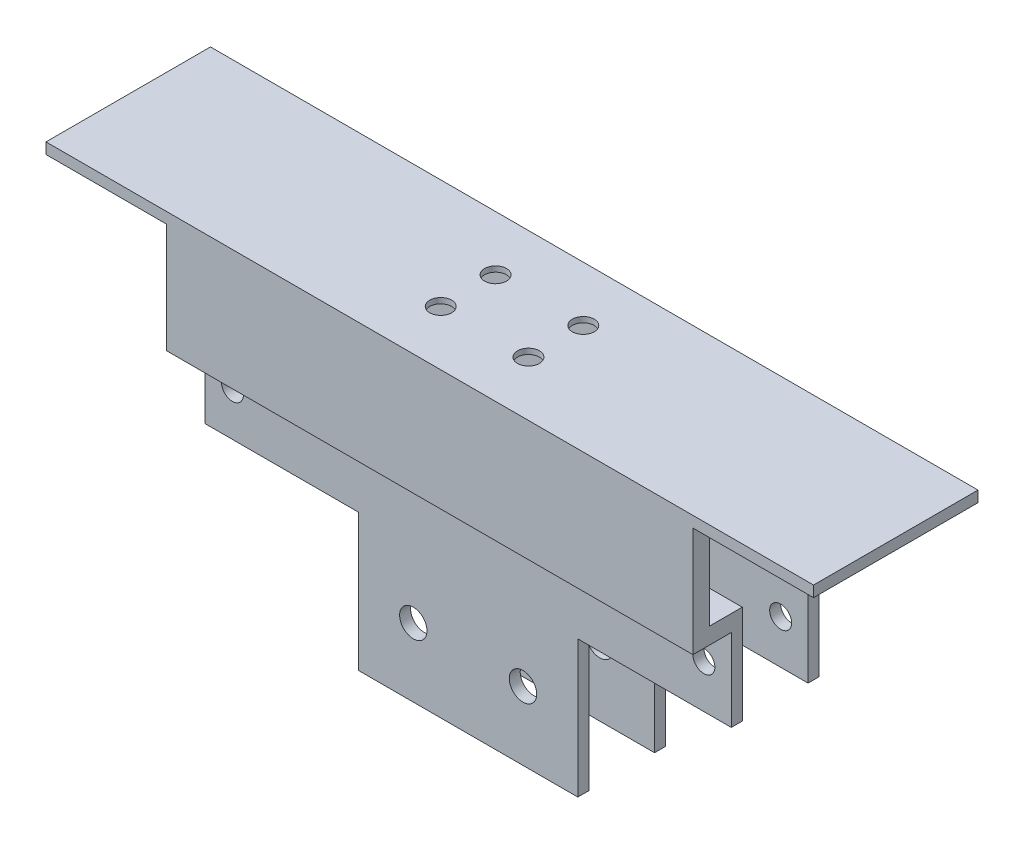
SolidWorks part; units mm, degrees
note: The reader was unsure of these and kept them because the rebuilt part matched: shared geometry of "Profile<3>", "Profile<6>", "Profile<7>", "Profile<8>", "Profile<9>", "Profile<10>", "Sketch3<3>".
ref_plane "Front Plane" through (0, 0, 0) normal (0, 0, 1) x (1, 0, 0)
ref_plane "Top Plane" through (0, 0, 0) normal (0, 1, 0) x (1, 0, 0)
ref_plane "Right Plane" through (0, 0, 0) normal (1, 0, 0) x (0, 0, -1)
sketch "Ref" plane through (0, 0, 0) normal (0, 1, 0) x (1, 0, 0)
  line L1 (-42.7409, 31.4353) -> (97.2591, 31.4353)
  line L2 (-42.7409, 31.4353) -> (-42.7409, 1.4353)
  line L3 (-42.7409, 1.4353) -> (97.2591, 1.4353)
  line L4 (97.2591, 31.4353) -> (97.2591, 1.4353)
  line L5 (-42.7409, 16.4353) -> (97.2591, 16.4353) construction
  point P8 (0, 0)
  dimension "D1" = 30
  dimension "D2" = 140
sketch "Profile" plane through (0, 0, 0) normal (0, 0, 1) x (1, 0, 0)
  line L0 (-32.7409, 0) -> (-32.7409, -35)
  line L1 (-42.7409, 0) -> (97.2591, 0) construction
  line L2 (-42.7409, 0) -> (97.2591, 0) construction
  line L3 (27.2591, 0) -> (27.2591, -85.3296) construction
  line L4 (27.2591, -60) -> (7.2591, -60)
  line L5 (7.2591, -60) -> (7.2591, -35)
  line L6 (7.2591, -35) -> (-32.7409, -35)
  line L7 (7.2591, -47.5) -> (47.2591, -47.5) construction
  line L8 (17.2591, -60) -> (17.2591, -35) construction
  line L9 (37.2591, -60) -> (37.2591, -35) construction
  line L10 (47.2591, -35) -> (87.2591, -35)
  line L11 (47.2591, -60) -> (47.2591, -35)
  line L12 (27.2591, -60) -> (47.2591, -60)
  line L13 (87.2591, 0) -> (87.2591, -35)
  line L14 (-32.7409, 0) -> (87.2591, 0)
  line L15 (-32.7409, 0) -> (-42.7409, 0)
  line L16 (-42.7409, 0) -> (97.2591, 0) construction
  line L17 (-42.7409, 0) -> (-42.7409, 2)
  line L18 (-42.7409, 2) -> (97.2591, 2)
  line L19 (97.2591, 2) -> (97.2591, 0)
  line L20 (97.2591, 0) -> (87.2591, 0)
  line L21 (-32.7409, -20) -> (87.2591, -20)
  line L22 (-32.7409, -17) -> (87.2591, -17)
  line L23 (-20.7409, -35) -> (-20.7409, 0)
  line L24 (75.2591, -35) -> (75.2591, 0)
  circle A0 centre (17.2591, -47.5) radius 2.5
  circle A1 centre (-15.7409, -27) radius 2
  circle A2 centre (70.2591, -27) radius 2
  circle A3 centre (37.2591, -47.5) radius 2.5
  point P22 (27.2591, -47.5)
  dimension "D5" = 5
  dimension "D6" = 4
  dimension "D1" = 35
  dimension "D2" = 60
  dimension "D3" = 20
  dimension "D4" = 60
  dimension "D7" = 43
  dimension "D8" = 27
  dimension "D9" = 2
  dimension "D10" = 20
  dimension "D11" = 3
  dimension "D12" = 12
extrude "Top" add sketch "Profile" against normal blind 30 contours L20 L19 L18 L17 L15 L14
extrude "Side" add sketch "Profile<3>" against normal blind 3 contours L0 L22 L13 L14
sketch "Profile<3>" plane through (0, 0, 0) normal (0, 0, 1) x (1, 0, 0) same geometry as "Profile"
extrude "Bend" add sketch "Profile<6>" against normal blind 9 contours L21 L24 L22 L23
sketch "Profile<6>" plane through (0, 0, 0) normal (0, 0, 1) x (1, 0, 0) same geometry as "Profile"
extrude "ScrewPlate" add sketch "Profile<7>" against normal blind 2 from offset 7 contours L10 L24 L21 L23 L6 L5 L4 L12 L11 A2 A1 A0 A3 offset against normal yes
sketch "Profile<7>" plane through (0, 0, 0) normal (0, 0, 1) x (1, 0, 0) same geometry as "Profile"
extrude "Side2" add sketch "Profile<8>" along normal blind 3 from offset 30 contours L22 L24 L14 L23 offset against normal yes
sketch "Profile<8>" plane through (0, 0, 0) normal (0, 0, 1) x (1, 0, 0) same geometry as "Profile"
extrude "Bend2" add sketch "Profile<9>" along normal blind 9 from offset 30 contours L21 L24 L22 L23 offset against normal yes
sketch "Profile<9>" plane through (0, 0, 0) normal (0, 0, 1) x (1, 0, 0) same geometry as "Profile"
extrude "ScrewPlate2" add sketch "Profile<10>" along normal blind 2 from offset 23 contours L10 L24 L21 L23 L6 L5 L4 L12 L11 A2 A1 A0 A3 offset against normal yes
sketch "Profile<10>" plane through (0, 0, 0) normal (0, 0, 1) x (1, 0, 0) same geometry as "Profile"
sketch "Sketch3" plane through (0, 2, 0) normal (0, 1, 0) x (1, 0, 0)
  line L0 (27.2591, 30) -> (27.2591, 0) construction
  line L1 (-42.7409, 30) -> (97.2591, 30) construction
  line L2 (-42.7409, 0) -> (97.2591, 0) construction
  line L3 (97.2591, 15) -> (-42.7409, 15) construction
  line L4 (97.2591, 30) -> (97.2591, 0) construction
  line L5 (-42.7409, 30) -> (-42.7409, 0) construction
  circle A0 centre (19.2591, 20) radius 2
  circle A1 centre (19.2591, 20) radius 4
  circle A2 centre (19.2591, 10) radius 2
  circle A3 centre (19.2591, 10) radius 4
  circle A4 centre (35.2591, 10) radius 4
  circle A5 centre (35.2591, 10) radius 2
  circle A6 centre (35.2591, 20) radius 4
  circle A7 centre (35.2591, 20) radius 2
  dimension "D1" = 4
  dimension "D4" = 8
  dimension "D2" = 5
  dimension "D3" = 8
extrude "Cut-Extrude4" cut sketch "Sketch3" against normal blind 2 contours A0 | A7 | A5 | A2
extrude "Cut-Extrude5" cut sketch "Sketch3<3>" against normal blind 1 from offset 1 contours A1 A0 | A6 A7 | A4 A5 | A3 A2
sketch "Sketch3<3>" plane through (0, 2, 0) normal (0, 1, 0) x (1, 0, 0) same geometry as "Sketch3"
